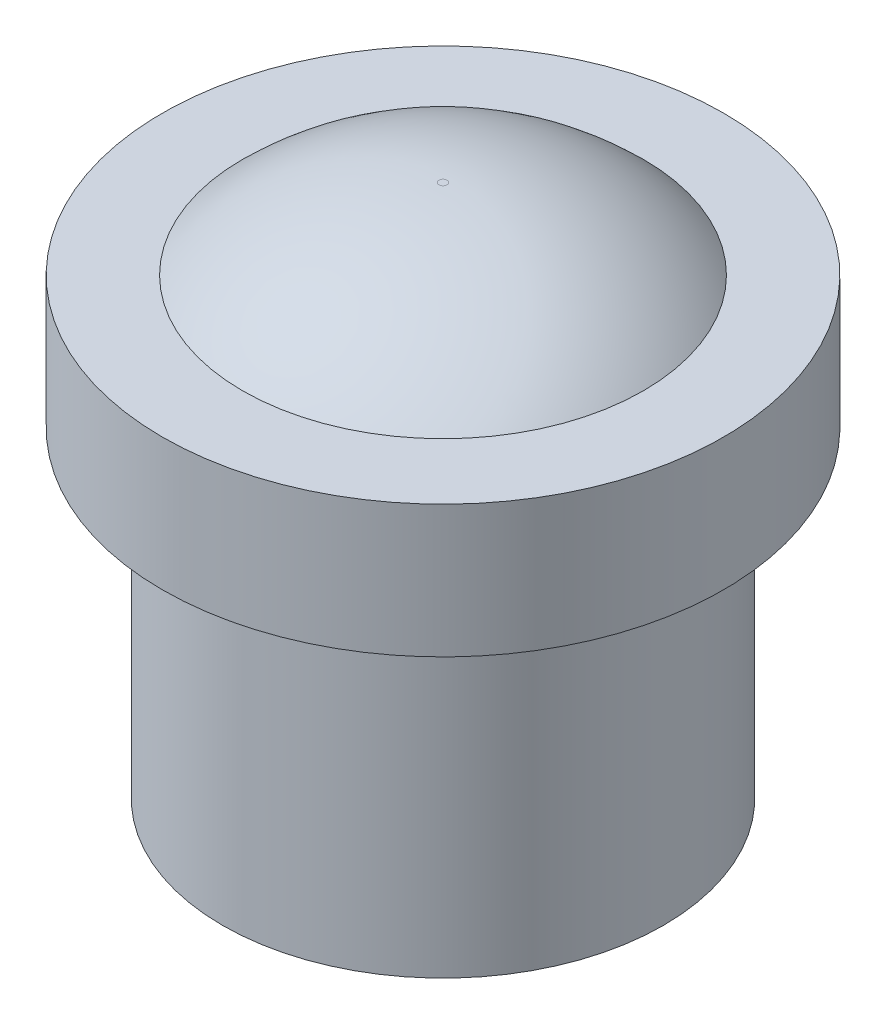
SolidWorks part; units mm, degrees
ref_plane "Front Plane" through (0, 0, 0) normal (0, 0, 1) x (1, 0, 0)
ref_plane "Top Plane" through (0, 0, 0) normal (0, 1, 0) x (1, 0, 0)
ref_plane "Right Plane" through (0, 0, 0) normal (1, 0, 0) x (0, 0, -1)
sketch "Sketch1" plane through (0, 0, 0) normal (0, 1, 0) x (1, 0, 0)
  circle A0 centre (0, 0) radius 7
  dimension "D1" = 14
extrude "Boss-Extrude1" add sketch "Sketch1" along normal blind 3.3
sketch "Sketch2" plane through (0, 0, 0) normal (0, -1, 0) x (1, 0, 0)
  circle A0 centre (0, 0) radius 5.5
  dimension "D1" = 11
extrude "Boss-Extrude2" add sketch "Sketch2" along normal blind 8
sketch "Sketch3" plane through (0, 3.3, 0) normal (0, 1, 0) x (1, 0, 0)
  circle A0 centre (0, 0) radius 5
  dimension "D1" = 10
extrude "Boss-Extrude3" add sketch "Sketch3" along normal blind 2
fillet "Fillet1" radius 7 1 edges at (0, 5.3, 5)
